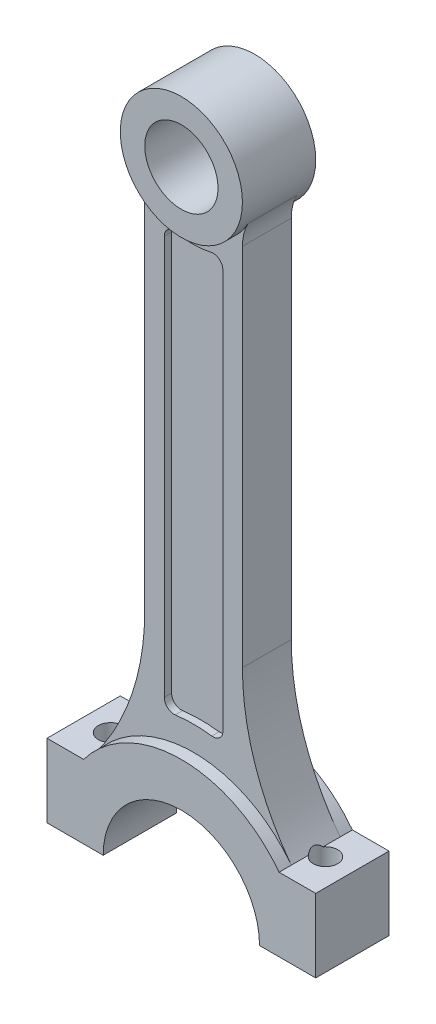
SolidWorks part; units mm, degrees
material "TIMETAL 35A CP Titanium (ASTM Grade 1) 99.1 Ti"
ref_plane "Front Plane" through (0, 0, 0) normal (0, 0, 1) x (1, 0, 0)
ref_plane "Top Plane" through (0, 0, 0) normal (0, 1, 0) x (1, 0, 0)
ref_plane "Right Plane" through (0, 0, 0) normal (1, 0, 0) x (0, 0, -1)
sketch "Sketch2" plane through (0, 0, 0) normal (0, 0, 1) x (1, 0, 0)
  line L0 (0, 0) -> (0, 130) construction
  line L1 (-27.5, 0) -> (-16, 0)
  line L2 (16, 0) -> (27.5, 0)
  line L3 (-27.5, 0) -> (-27.5, 15)
  line L4 (-27.5, 15) -> (-20, 15)
  line L6 (-10, 122.5) -> (-10, 45)
  line L8 (27.5, 0) -> (27.5, 15)
  line L9 (27.5, 15) -> (20, 15)
  line L12 (10, 122.5) -> (10, 45)
  circle A0 centre (0, 0) radius 16 construction
  circle A1 centre (0, 130) radius 7.5
  arc A2 (10, 122.5) -> (-10, 122.5) centre (0, 130) ccw
  circle A3 centre (0, 0) radius 25 construction
  arc A4 (-16, 0) -> (16, 0) centre (0, 0) cw
  arc A7 (-10, 45) -> (-20, 15) centre (-60, 45) cw
  arc A8 (10, 45) -> (20, 15) centre (60, 45) ccw
  point P19 (10, 39.7244)
  point P22 (0, 0)
  dimension "D2" = 32
  dimension "D3" = 15
  dimension "D4" = 25
  dimension "D5" = 50
  dimension "D1" = 130
  dimension "D6" = 55
  dimension "D7" = 20
  dimension "D8" = 15
  dimension "D10" = 10
extrude "Boss-Extrude1" add sketch "Sketch2" along normal blind 5 and the other way blind 5
sketch "Sketch3" plane through (0, 0, 0) normal (0, 0, 1) x (1, 0, 0)
  line L0 (16, 0) -> (27.5, 0) construction
  line L5 (-27.5, 15) -> (-27.5, 0)
  line L6 (-27.5, 0) -> (-16, 0)
  line L11 (27.5, 0) -> (16, 0)
  line L12 (-27.5, 15) -> (-20, 15)
  line L13 (20, 15) -> (27.5, 15)
  line L14 (27.5, 15) -> (27.5, 0)
  arc A0 (-16, 0) -> (16, 0) centre (0, 0) cw
  arc A1 (16, 0) -> (-16, 0) centre (0, 0) ccw construction
  arc A2 (-20, 15) -> (20, 15) centre (0, 0) cw
  circle A3 centre (0, 0) radius 25 construction
  circle A4 centre (0, 0) radius 16 construction
extrude "Boss-Extrude2" add sketch "Sketch3" along normal blind 7.5 and the other way blind 7.5
sketch "Sketch5" plane through (0, 0, 0) normal (0, 0, 1) x (1, 0, 0)
  circle A0 centre (0, 130) radius 12.5
  circle A1 centre (0, 130) radius 7.5
extrude "Boss-Extrude3" add sketch "Sketch5" along normal blind 7.5 and the other way blind 7.5
sketch "Sketch6" plane through (0, 0, 5) normal (0, 0, 1) x (1, 0, 0)
  line L0 (-6, 31.749) -> (-6, 113.4773)
  line L1 (0, 0) -> (0, 130) construction
  line L2 (-10, 122.5) -> (-10, 45) construction
  line L3 (6, 31.749) -> (6, 113.4773)
  arc A0 (-3.5294, 115.4211) -> (3.5294, 115.4211) centre (0, 130) ccw
  arc A1 (3.75, 29.7647) -> (-3.75, 29.7647) centre (0, 0) ccw
  arc A2 (6, 113.4773) -> (3.5294, 115.4211) centre (4, 113.4773) ccw
  arc A3 (-6, 113.4773) -> (-3.5294, 115.4211) centre (-4, 113.4773) cw
  arc A4 (6, 31.749) -> (3.75, 29.7647) centre (4, 31.749) cw
  arc A5 (-6, 31.749) -> (-3.75, 29.7647) centre (-4, 31.749) ccw
  arc A6 (20, 15) -> (-20, 15) centre (0, 0) ccw construction
  point P12 (6, 116.2523)
  point P15 (-6, 116.2523)
  point P18 (6, 29.3939)
  point P21 (-6, 29.3939)
  dimension "D1" = 15
  dimension "D2" = 30
  dimension "D4" = 2
  dimension "D3" = 4
extrude "Cut-Extrude1" cut sketch "Sketch6" against normal blind 1.5
mirror "Mirror1" about plane through (0, 0, 0) normal (0, 0, 1) of "Cut-Extrude1"
fillet "Fillet1" radius 10 2 edges at (-10, 122.5, 0) (10, 122.5, 0)
sketch "Sketch7" plane through (0, 0, 0) normal (0, -1, 0) x (1, 0, 0)
  circle A0 centre (-22, 0) radius 3
  circle A1 centre (22, 0) radius 3
  dimension "D1" = 6
  dimension "D3" = 22
  dimension "D2" = 22
hole_wizard "Tap Drill for M6 Tap1" positions "Sketch8" profile "Sketch10" hole size "M6" standard "ISO" end condition through all
sketch "Sketch8" plane through (0, 0, 0) normal (0, -1, 0) x (-1, 0, 0)
  point P0 (22, 0)
  point P3 (-22, 0)
sketch "Sketch10" plane through (-22, 0, 0) normal (1, 0, 0) x (0, 0, -1)
  line L0 (0, 0) -> (0, 142.5)
  line L1 (0, 142.5) -> (2.5, 142.5)
  line L2 (2.5, 142.5) -> (2.5, 0)
  line L5 (2.5, 0) -> (0, 0)
  line L11 (0, -6.35) -> (0, 107.95) construction
  dimension "Thru Hole Dia." = 5
  dimension "Thru Hole Depth" = 142.5
